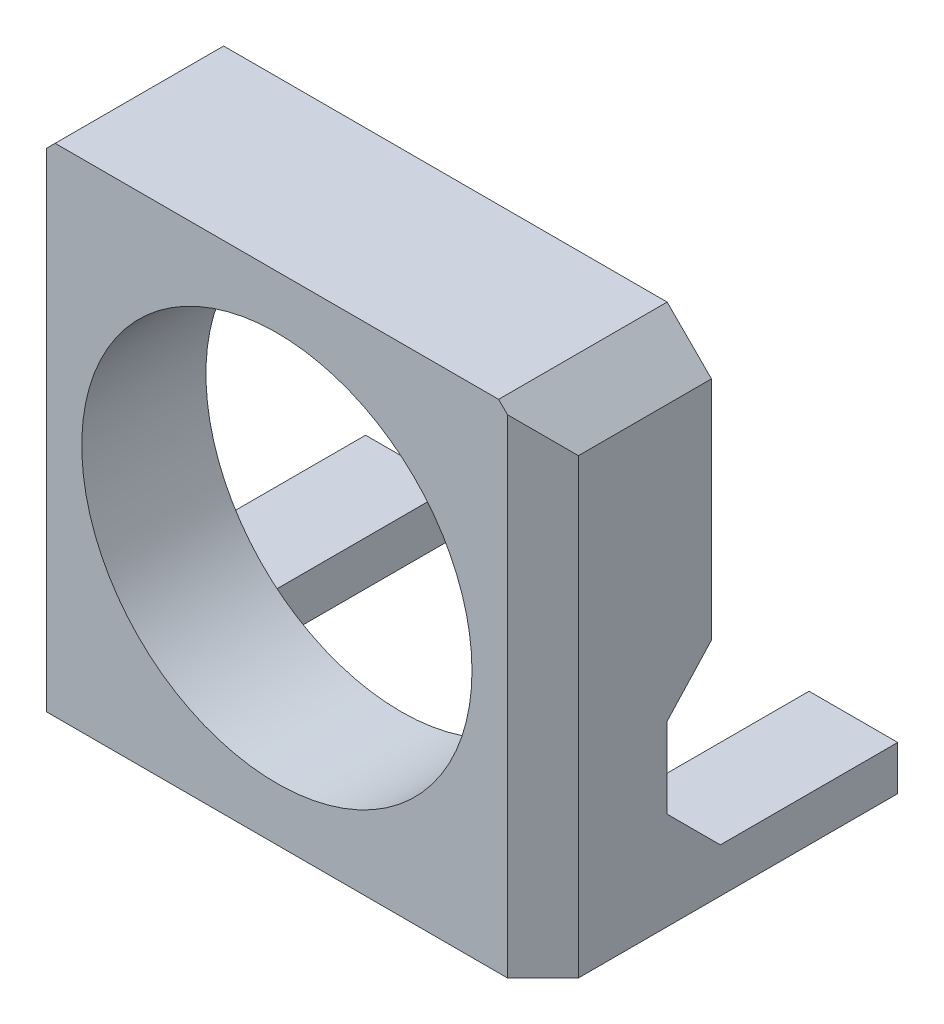
SolidWorks part; units mm, degrees
ref_plane "Front Plane" through (0, 0, 0) normal (0, 0, 1) x (1, 0, 0)
ref_plane "Top Plane" through (0, 0, 0) normal (0, 1, 0) x (1, 0, 0)
ref_plane "Right Plane" through (0, 0, 0) normal (1, 0, 0) x (0, 0, -1)
sketch "Sketch1" plane through (0, 0, 0) normal (0, 0, 1) x (1, 0, 0)
  line L0 (-15, 11.5) -> (-12.5, 14)
  line L1 (-12.5, 14) -> (12.5, 14)
  line L2 (-15, 11.5) -> (-15, -14)
  line L3 (-15, -14) -> (15, -14)
  line L4 (15, 11.5) -> (15, -14)
  line L5 (-15, 14) -> (15, -14) construction
  line L6 (-15, -14) -> (15, 14) construction
  line L7 (12.5, 14) -> (15, 11.5)
  circle A0 centre (0, 0) radius 11
  dimension "D1" = 22
  dimension "D2" = 30
  dimension "D3" = 28
extrude "Boss-Extrude1" add sketch "Sketch1" along normal blind 7
sketch "Sketch2" plane through (0, 0, 0) normal (0, 0, -1) x (-1, 0, 0)
  line L0 (0, 0) -> (0, -50000) construction
  line L1 (-15, -14) -> (-10, -14)
  line L2 (-15, -14) -> (-15, -11.5)
  line L3 (-15, -11.5) -> (-10, -11.5)
  line L4 (-10, -14) -> (-10, -11.5)
  line L5 (15, -11.5) -> (10, -11.5)
  line L6 (10, -14) -> (10, -11.5)
  line L7 (15, -14) -> (10, -14)
  line L8 (15, -14) -> (15, -11.5)
  dimension "D1" = 2.5
  dimension "D2" = 5
extrude "Boss-Extrude2" add sketch "Sketch2" along normal blind 13 contours L5 L6 L7 L8 | L2 L3 L4 L1
chamfer "Chamfer1" distance 3 2 edges at (-12.5, -11.5, 0) (12.5, -11.5, 0)
chamfer "Chamfer2" distance 2 angle 45 2 edges at (-10, -11.25, 0) (10, -11.25, 0)
chamfer "Chamfer3" distance 2 angle 45 1 edges at (15, -1.25, 7)
chamfer "Chamfer4" distance 2 angle 45 1 edges at (-15, -1.25, 7)
sketch "Sketch4" plane through (0, 0, 0) normal (0, 0, -1) x (-1, 0, 0)
  line L8 (0, 0) -> (0, 50000) construction
  line L14 (-15, -1.25) -> (15, 11.5)
  line L15 (15, 11.5) -> (12.5, 14)
  line L16 (12.5, 14) -> (-12.5, 14)
  line L17 (-12.5, 14) -> (-15, 11.5)
  line L18 (-15, 11.5) -> (-15, -1.25)
  line L19 (-15, 11.5) -> (-15, -14) construction
  point P8 (-15, -1.25)
extrude "Boss-Extrude4" add sketch "Sketch4" along normal blind 2.5
chamfer "Chamfer6" distance 2.5 2 edges at (12.9953, -0.398, 0) (-11.1504, 9.8639, 0)
